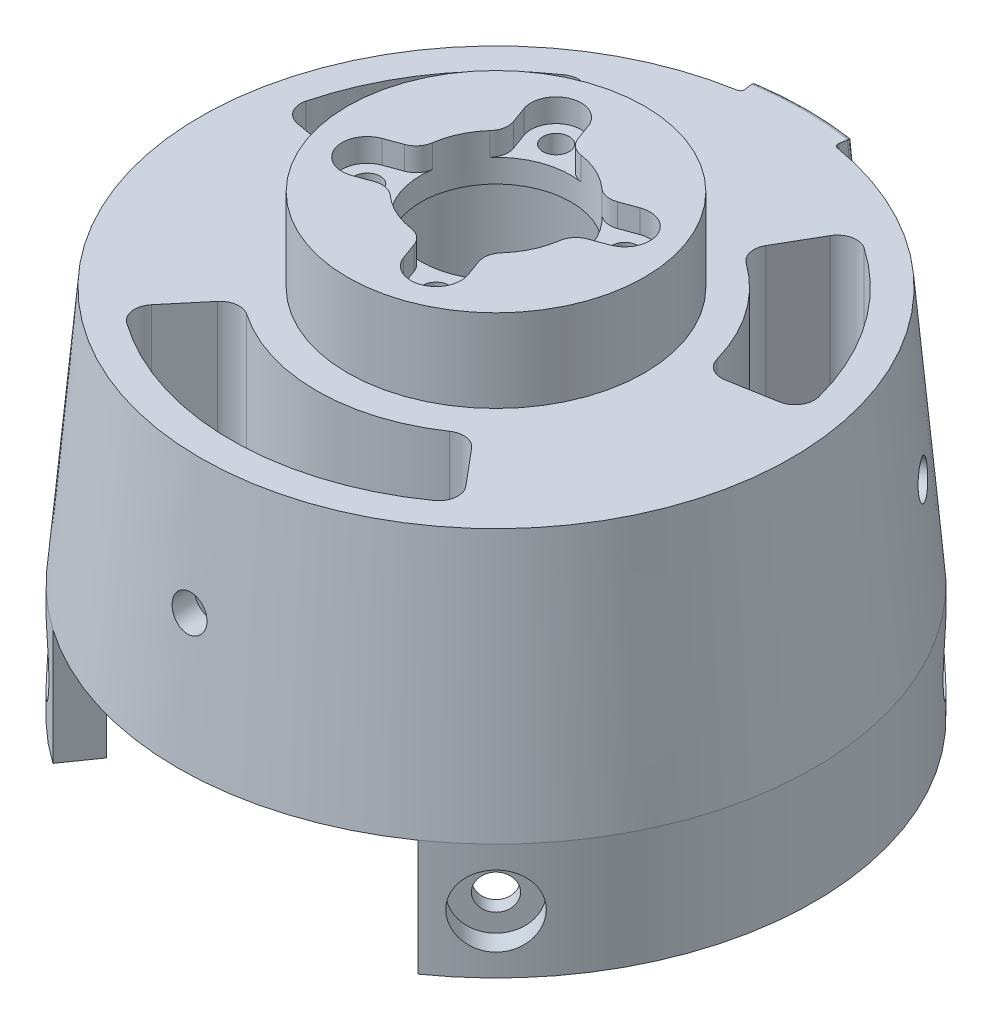
SolidWorks part; units mm, degrees
ref_plane "Front Plane" through (0, 0, 0) normal (0, 0, 1) x (1, 0, 0)
ref_plane "Top Plane" through (0, 0, 0) normal (0, 1, 0) x (1, 0, 0)
ref_plane "Right Plane" through (0, 0, 0) normal (1, 0, 0) x (0, 0, -1)
sketch "Sketch1" plane through (0, 0, 0) normal (0, 1, 0) x (1, 0, 0)
  line L0 (-29.85, 23.9174) -> (-29.85, -23.9174)
  line L1 (29.85, 23.9174) -> (29.85, -23.9174)
  line L2 (-29.85, 0) -> (29.85, 0) construction
  arc A0 (-29.85, -23.9174) -> (29.85, -23.9174) centre (0, 0) ccw
  arc A1 (29.85, 23.9174) -> (-29.85, 23.9174) centre (0, 0) ccw
  point P9 (0, 0)
  dimension "D1" = 59.7
  dimension "D2" = 76.5
extrude "Boss-Extrude1" add sketch "Sketch1" along normal blind 44
sketch "Sketch2" plane through (0, 44, 0) normal (0, 1, 0) x (1, 0, 0)
  line L0 (-4.4463, 12.216) -> (0, 0) construction
  line L1 (0, 13) -> (0, 0) construction
  circle A0 centre (0, 0) radius 13
  point P3 (-4.4463, 12.216)
  dimension "D1" = 26
  dimension "D2" = 20
hole_wizard "CBORE for M3 SHCS1" positions "Sketch2" profile "Sketch3" counterbore size "M3" standard "ANSI Metric" end condition through all
sketch "Sketch3" plane through (-4.4463, 44, -12.216) normal (1, 0, 0) x (0, 0, 1)
  line L0 (0, 0) -> (0, 44)
  line L1 (0, 44) -> (1.7, 44)
  line L3 (1.7, 44) -> (1.7, 3)
  line L4 (1.7, 3) -> (3.25, 3)
  line L5 (3.25, 3) -> (3.25, 0)
  line L7 (3.25, 0) -> (0, 0)
  line L11 (0, -6.35) -> (0, 107.95) construction
  dimension "Thru Hole Dia." = 3.4
  dimension "Thru Hole Depth" = 44
  dimension "C'Bore Dia." = 6.5
  dimension "C'Bore Depth" = 3
ref_axis "Axis1" through (0, 44, 0) along (0, -1, 0)
pattern_circular "CirPattern1" count 4 over 360 about axis through (0, 44, 0) along (0, -1, 0) of "CBORE for M3 SHCS1"
sketch "Sketch4" plane through (0, 0, 0) normal (0, -1, 0) x (1, 0, 0)
  circle A0 centre (0, 0) radius 16.2
  dimension "D1" = 32.4
extrude "Cut-Extrude1" cut sketch "Sketch4" against normal blind 38
sketch "Sketch5" plane through (0, 44, 0) normal (0, 1, 0) x (1, 0, 0)
  circle A0 centre (0, 0) radius 9.7
extrude "Cut-Extrude2" cut sketch "Sketch5" against normal through all
ref_plane "Plane1" through (0, 0, -38.25) normal (0, 0, -1) x (-1, 0, 0)
sketch "Sketch7" plane through (0, 0, 0) normal (0, -1, 0) x (1, 0, 0)
  line L5 (29.85, 23.9174) -> (29.85, -23.9174)
  line L6 (-29.85, 23.9174) -> (-29.85, -23.9174)
  arc A0 (-29.85, -23.9174) -> (29.85, -23.9174) centre (0, 0) ccw construction
  arc A1 (29.85, 23.9174) -> (-29.85, 23.9174) centre (0, 0) ccw construction
  arc A2 (-29.85, -23.9174) -> (29.85, -23.9174) centre (0, 0) ccw
  arc A3 (29.85, 23.9174) -> (-29.85, 23.9174) centre (0, 0) ccw
  circle A4 centre (0, 0) radius 41.1622
  dimension "D1" = 82.3245
extrude "Boss-Extrude2" add sketch "Sketch7" against normal up to surface (44 mm away) up to face at (0, 44, 9.7)
sketch "Sketch9" plane through (0, 0, 0) normal (1, 0, 0) x (0, 0, -1)
  line L0 (-41.1622, 0) -> (-37.3127, 44)
  line L1 (-37.3127, 44) -> (-41.1622, 44)
  line L2 (-41.1622, 44) -> (-41.1622, 0) construction
  line L3 (-41.1622, 44) -> (-41.1622, 0)
  line L4 (0, 0) -> (0, 44) construction
  line L5 (41.1622, 44) -> (-41.1622, 44) construction
  dimension "D1" = 5
revolve "Cut-Revolve2" cut sketch "Sketch9" angle 360 about L4
sketch "Sketch10" plane through (0, 0, 0) normal (1, 0, 0) x (0, 0, -1)
  line L0 (-19.2, 44) -> (-19.2, 33.2871)
  line L1 (37.3127, 44) -> (-37.3127, 44) construction
  line L2 (-19.2, 33.2871) -> (-38.25, 33.2871)
  line L3 (-37.3127, 44) -> (-41.1622, 0) construction
  line L4 (-38.25, 33.2871) -> (-37.3127, 44)
  line L5 (-37.3127, 44) -> (-19.2, 44)
  line L6 (0, 0) -> (0, 44) construction
  line L10 (-41.1622, 0) -> (41.1622, 0) construction
  line L11 (-16.2, 0) -> (16.2, 0) construction
  line L12 (-16.2, 0) -> (16.2, 0) construction
  line L13 (37.3127, 44) -> (-37.3127, 44) construction
  dimension "D1" = 10.7129
  dimension "D2" = 33.2871
  dimension "D3" = 3
revolve "Cut-Revolve3" cut sketch "Sketch10" angle 360 about L6
sketch "Sketch13" plane through (0, 33.2871, 0) normal (0, 1, 0) x (1, 0, 0)
  line L0 (0, -34.25) -> (0, -38.25) construction
  circle A0 centre (0, 0) radius 34.25
  circle A1 centre (0, 0) radius 19.2 construction
  circle A2 centre (0, 0) radius 19.2
  circle A3 centre (0, 0) radius 38.25 construction
  dimension "D1" = 4
extrude "Cut-Extrude3" cut sketch "Sketch13" against normal through all both and the other way through all
sketch "Sketch16" plane through (0, 0, 0) normal (0, -1, 0) x (1, 0, 0)
  line L0 (0, -34.25) -> (0, -19.2) construction
  line L1 (-17.125, -29.6614) -> (-9.6, -16.6277)
  line L2 (17.125, -29.6614) -> (9.6, -16.6277)
  line L3 (-33.7297, -5.9475) -> (-18.9083, -3.334)
  line L4 (-22.0155, 26.237) -> (-12.3415, 14.7081)
  line L5 (22.0155, 26.237) -> (12.3415, 14.7081)
  line L6 (33.7297, -5.9475) -> (18.9083, -3.334)
  line L7 (0, 0) -> (-32.1845, 11.7142) construction
  circle A1 centre (0, 0) radius 34.25 construction
  circle A2 centre (0, 0) radius 19.2 construction
  arc A3 (-9.6, -16.6277) -> (9.6, -16.6277) centre (0, 0) ccw
  arc A4 (-17.125, -29.6614) -> (17.125, -29.6614) centre (0, 0) ccw
  arc A5 (-22.0155, 26.237) -> (-33.7297, -5.9475) centre (0, 0) ccw
  arc A6 (-12.3415, 14.7081) -> (-18.9083, -3.334) centre (0, 0) ccw
  arc A7 (22.0155, 26.237) -> (33.7297, -5.9475) centre (0, 0) cw
  arc A8 (12.3415, 14.7081) -> (18.9083, -3.334) centre (0, 0) cw
  point P19 (0, 0)
  dimension "D1" = 15.05
  dimension "D3" = 60
  dimension "D4" = 110
  dimension "D2" = 2
extrude "Boss-Extrude4" add sketch "Sketch16" against normal up to surface (33.2871 mm away) up to face at (0, 33.2871, 34.25)
sketch "Sketch17" plane through (0, 33.2871, 0) normal (0, 1, 0) x (1, 0, 0)
  line L0 (0, -19.2) -> (0, -23.2) construction
  circle A0 centre (0, 0) radius 23.2
  circle A1 centre (0, 0) radius 19.2 construction
  circle A2 centre (0, 0) radius 19.2
  dimension "D1" = 4
extrude "Boss-Extrude5" add sketch "Sketch17" against normal up to surface (33.2871 mm away) up to face at (-20.8663, 0, -14.6107)
fillet "Fillet2" radius 2.5 12 edges at (-14.9127, 16.6435, 17.7722) (-22.0155, 16.6435, 26.237) (22.0155, 16.6435, 26.237) (14.9127, 16.6435, 17.7722) (-17.125, 16.6435, -29.6614) (-33.7297, 16.6435, -5.9475) (-22.8475, 16.6435, -4.0286) (-11.6, 16.6435, -20.0918) (33.7297, 16.6435, -5.9475) (17.125, 16.6435, -29.6614) (11.6, 16.6435, -20.0918) (22.8475, 16.6435, -4.0286)
ref_plane "Plane2" through (0, 16.6435, 0) normal (0, -1, 0) x (-1, 0, 0)
sketch "Sketch18" plane through (0, 16.6435, 0) normal (0, -1, 0) x (-1, 0, 0)
  line L0 (0, 0) -> (28.056, 19.645) construction
  line L1 (0, 0) -> (-28.056, 19.645) construction
  line L2 (0, 0) -> (0, -34.25) construction
  line L3 (0, 0) -> (-10.437, -32.621) construction
  line L4 (0, 0) -> (10.437, -32.621) construction
  arc A0 (33.1566, 8.5849) -> (19.4074, 28.2209) centre (0, 0) ccw construction
  arc A1 (-19.4074, 28.2209) -> (-33.1566, 8.5849) centre (0, 0) ccw construction
  arc A2 (-19.8812, -27.8891) -> (19.8812, -27.8891) centre (0, 0) ccw construction
  arc A3 (-19.8812, -27.8891) -> (0, -34.25) centre (0, 0) ccw construction
  arc A4 (0, -34.25) -> (19.8812, -27.8891) centre (0, 0) ccw construction
ref_plane "Plane4" through (-28.056, 16.6435, -19.645) normal (-0.8192, 0, -0.5736) x (-0.5736, 0, 0.8192)
sketch "Sketch20" plane through (-28.056, 16.6435, -19.645) normal (-0.8192, 0, -0.5736) x (-0.5736, 0, 0.8192)
  circle A0 centre (0, 0) radius 2.25
  dimension "D1" = 4.5
extrude "Cut-Extrude5" cut sketch "Sketch20" against normal blind 10 and the other way through all
sketch "Sketch21" plane through (-28.056, 16.6435, -19.645) normal (-0.8192, 0, -0.5736) x (-0.5736, 0, 0.8192)
  line L1 (4.0415, 0) -> (2.0207, 3.5)
  line L2 (2.0207, 3.5) -> (-2.0207, 3.5)
  line L3 (-2.0207, 3.5) -> (-4.0415, 0)
  line L4 (-4.0415, 0) -> (-2.0207, -3.5)
  line L5 (-2.0207, -3.5) -> (2.0207, -3.5)
  line L6 (2.0207, -3.5) -> (4.0415, 0)
  circle A0 centre (0, 0) radius 3.5 construction
  dimension "D1" = 4.0415
  dimension "D2" = 7
extrude "Cut-Extrude6" cut sketch "Sketch21" against normal blind 10 and the other way blind 2.5
pattern_circular "CirPattern2" count 3 over 250 about axis through (0, 0, 0) along (0, 1, 0) of "Cut-Extrude5", "Cut-Extrude6"
sketch "Sketch22" plane through (0, 44, 0) normal (0, 1, 0) x (1, 0, 0)
  line L2 (-12.216, -4.4463) -> (12.216, 4.4463) construction
  line L3 (-13.3276, -1.3923) -> (11.1044, 7.5003) construction
  line L4 (-11.1044, -7.5003) -> (13.3276, 1.3923) construction
  line L5 (-4.4463, 12.216) -> (4.4463, -12.216) construction
  line L6 (-1.3923, 13.3276) -> (7.5003, -11.1044) construction
  line L7 (-7.5003, 11.1044) -> (1.3923, -13.3276) construction
  line L8 (-11.1044, -7.5003) -> (-1.9424, -4.1656)
  line L9 (-1.9424, -4.1656) -> (1.3923, -13.3276)
  line L10 (7.5003, -11.1044) -> (4.1656, -1.9424)
  line L11 (4.1656, -1.9424) -> (13.3276, 1.3923)
  line L12 (11.1044, 7.5003) -> (1.9424, 4.1656)
  line L13 (1.9424, 4.1656) -> (-1.3923, 13.3276)
  line L14 (-7.5003, 11.1044) -> (-4.1656, 1.9424)
  line L15 (-4.1656, 1.9424) -> (-13.3276, -1.3923)
  arc A0 (-13.3276, -1.3923) -> (-11.1044, -7.5003) centre (-12.216, -4.4463) ccw
  arc A1 (1.3923, -13.3276) -> (7.5003, -11.1044) centre (4.4463, -12.216) ccw
  arc A2 (13.3276, 1.3923) -> (11.1044, 7.5003) centre (12.216, 4.4463) ccw
  arc A3 (-1.3923, 13.3276) -> (-7.5003, 11.1044) centre (-4.4463, 12.216) ccw
  arc A10 (-13.3276, -1.3923) -> (-11.1044, -7.5003) centre (-12.216, -4.4463) ccw construction
  arc A11 (13.3276, 1.3923) -> (11.1044, 7.5003) centre (12.216, 4.4463) ccw construction
  circle A12 centre (12.216, 4.4463) radius 3.25 construction
  arc A13 (-1.3923, 13.3276) -> (-7.5003, 11.1044) centre (-4.4463, 12.216) ccw construction
  arc A14 (1.3923, -13.3276) -> (7.5003, -11.1044) centre (4.4463, -12.216) ccw construction
  circle A15 centre (4.4463, -12.216) radius 3.25 construction
  point P2 (0, 0)
  point P11 (0, 0)
extrude "temporary_probnably" cut sketch "Sketch22" against normal up to surface (3 mm away) up to face at (-4.4463, 41, -10.516)
fillet "also_probably_temporary" radius 2.5 8 edges at (-9.6997, 42.5, 0.0718) (-7.4766, 42.5, 6.1798) (0.0718, 42.5, 9.6997) (6.1798, 42.5, 7.4766) (9.6997, 42.5, -0.0718) (7.4766, 42.5, -6.1798) (-0.0718, 42.5, -9.6997) (-6.1798, 42.5, -7.4766)
sketch "Sketch24" plane through (0, 0, 0) normal (1, 0, 0) x (0, 0, -1)
  line L0 (38.25, 33.2871) -> (-38.25, 33.2871) construction
  line L1 (-41.1622, 0) -> (41.1622, 0) construction
  line L2 (38.25, 33.2871) -> (-38.25, 33.2871) construction
  line L3 (-41.1622, 0) -> (41.1622, 0) construction
  line L4 (41.1622, 0) -> (43.1622, 0)
  line L5 (38.25, 33.2871) -> (40.25, 33.2871)
  line L6 (38.25, 33.2871) -> (41.1622, 0)
  line L7 (40.25, 33.2871) -> (43.1622, 0)
  line L8 (0, 33.2871) -> (0, 0) construction
  dimension "D1" = 2
revolve "key_1" add sketch "Sketch24" angle 9 about L8 other way angle 9
fillet "key_2" radius 0.5 6 edges at (0, 0, -43.1622) (0, 33.2871, -40.25) (-6.5243, 16.6435, -41.1926) (6.5243, 16.6435, -41.1926) (-6.2114, 16.6435, -39.2173) (6.2114, 16.6435, -39.2173)
sketch "Sketch25" plane through (0, 0, 0) normal (0, -1, 0) x (1, 0, 0)
  line L0 (-23.6097, -33.7181) -> (23.6097, 33.7181) construction
  line L1 (23.6097, -33.7181) -> (-23.6097, 33.7181) construction
  line L2 (-20.7418, 29.6224) -> (-23.6097, 33.7181)
  line L3 (-20.7418, -29.6224) -> (-23.6097, -33.7181)
  line L4 (0, 0) -> (0, 41.1622) construction
  line L6 (20.7418, 29.6224) -> (23.6097, 33.7181)
  line L7 (20.7418, -29.6224) -> (23.6097, -33.7181)
  arc A1 (-23.6097, 33.7181) -> (-23.6097, -33.7181) centre (0, 0) ccw
  circle A3 centre (0, 0) radius 36.1622 construction
  arc A4 (6.9267, -40.5753) -> (-6.9267, -40.5753) centre (0, 0) ccw construction
  arc A7 (-20.7418, -29.6224) -> (-20.7418, 29.6224) centre (0, 0) cw
  arc A20 (6.9267, -40.5753) -> (-6.9267, -40.5753) centre (0, 0) ccw construction
  arc A21 (20.7418, -29.6224) -> (20.7418, 29.6224) centre (0, 0) ccw
  arc A22 (23.6097, 33.7181) -> (23.6097, -33.7181) centre (0, 0) cw
  point P14 (0, 36.1622)
  point P16 (0, 36.1622)
  dimension "D1" = 70
  dimension "D2" = 5
extrude "Boss-Extrude6" add sketch "Sketch25" along normal blind 15
ref_plane "Plane5" through (0, -7.5, 0) normal (0, -1, 0) x (-1, 0, 0)
sketch "Sketch26" plane through (0, -7.5, 0) normal (0, -1, 0) x (-1, 0, 0)
  line L0 (0, 0) -> (41.1622, 0) construction
  line L1 (0, 0) -> (29.1061, -29.1061) construction
  arc A0 (23.6097, -33.7181) -> (23.6097, 33.7181) centre (0, 0) ccw construction
  dimension "D1" = 45
ref_plane "Plane6" through (-29.1061, -7.5, 29.1061) normal (-0.7071, 0, 0.7071) x (0.7071, 0, 0.7071)
sketch "Sketch28" plane through (-29.1061, -7.5, 29.1061) normal (-0.7071, 0, 0.7071) x (0.7071, 0, 0.7071)
  circle A0 centre (0, 0) radius 2.25
  dimension "D1" = 4.5
extrude "Cut-Extrude7" cut sketch "Sketch28" along normal through all and the other way up to surface other way up to face at (28.452, -7.5, 0)
sketch "Sketch29" plane through (-29.1061, -7.5, 29.1061) normal (-0.7071, 0, 0.7071) x (0.7071, 0, 0.7071)
  circle A0 centre (0, 0) radius 2.25 construction
  circle A1 centre (0, 0) radius 2.25
  circle A2 centre (0, 0) radius 4.6
  dimension "D1" = 9.2
extrude "Cut-Extrude8" cut sketch "Sketch29" against normal blind 3
mirror "Mirror1" about plane through (0, 0, 0) normal (0, 0, 1) of "Cut-Extrude8", "Cut-Extrude7"
mirror "Mirror2" about plane through (0, 0, 0) normal (1, 0, 0) of "Mirror1"
